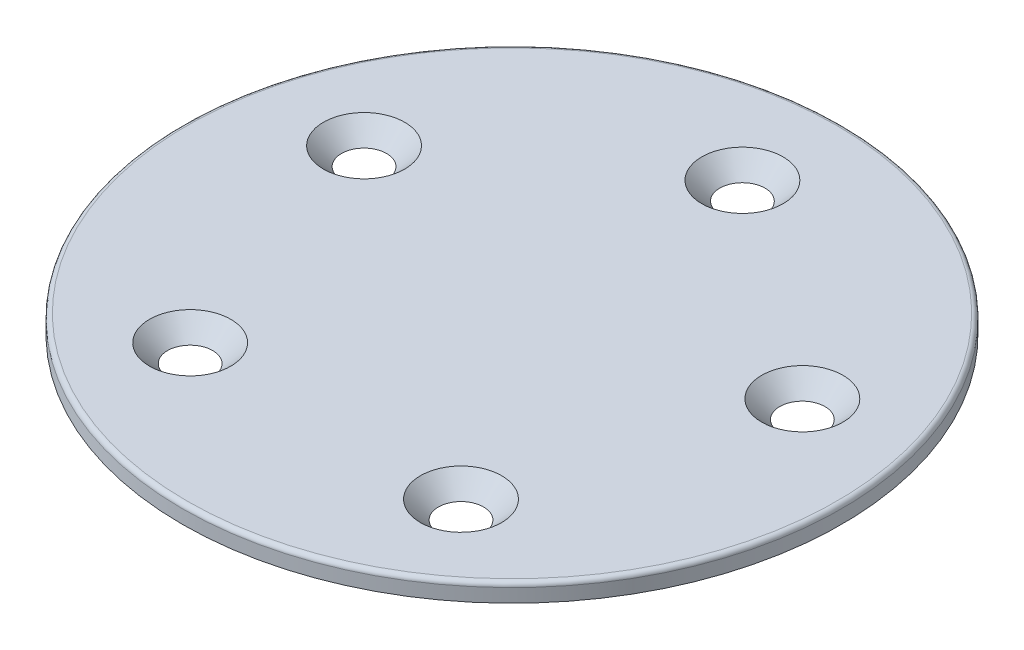
SolidWorks part; units mm, degrees
ref_plane "Front Plane" through (0, 0, 0) normal (0, 0, 1) x (1, 0, 0)
ref_plane "Top Plane" through (0, 0, 0) normal (0, 1, 0) x (1, 0, 0)
ref_plane "Right Plane" through (0, 0, 0) normal (1, 0, 0) x (0, 0, -1)
sketch "Sketch2" plane through (0, 0, 0) normal (0, 1, 0) x (1, 0, 0)
  circle A0 centre (0, 0) radius 36.5
  circle A1 centre (0, 0) radius 25.52 construction
  circle A2 centre (0, 25.52) radius 2.5
  circle A3 centre (24.271, 7.8861) radius 2.5
  circle A4 centre (15.0003, -20.6461) radius 2.5
  circle A5 centre (-15.0003, -20.6461) radius 2.5
  circle A6 centre (-24.271, 7.8861) radius 2.5
  point P16 (0, 0)
  dimension "D1" = 73
  dimension "D2" = 51.04
  dimension "D4" = 5
  dimension "D3" = 5
extrude "Boss-Extrude1" add sketch "Sketch2" along normal blind 2 contours A0 A6 A1 A2 A3 A4 A5 | A6 A1 A5 A4 A3 A2 region at (-35.4676, 0, 0) region at (0, 0, 0)
chamfer "Chamfer1" distance 2 5 edges at (-15.0003, 2, 23.1461) (15.0003, 2, 23.1461) (24.271, 2, -5.3861) (0, 2, -23.02) (-24.271, 2, -5.3861)
fillet "Fillet1" radius 0.5 1 edges at (0, 2, 36.5)
